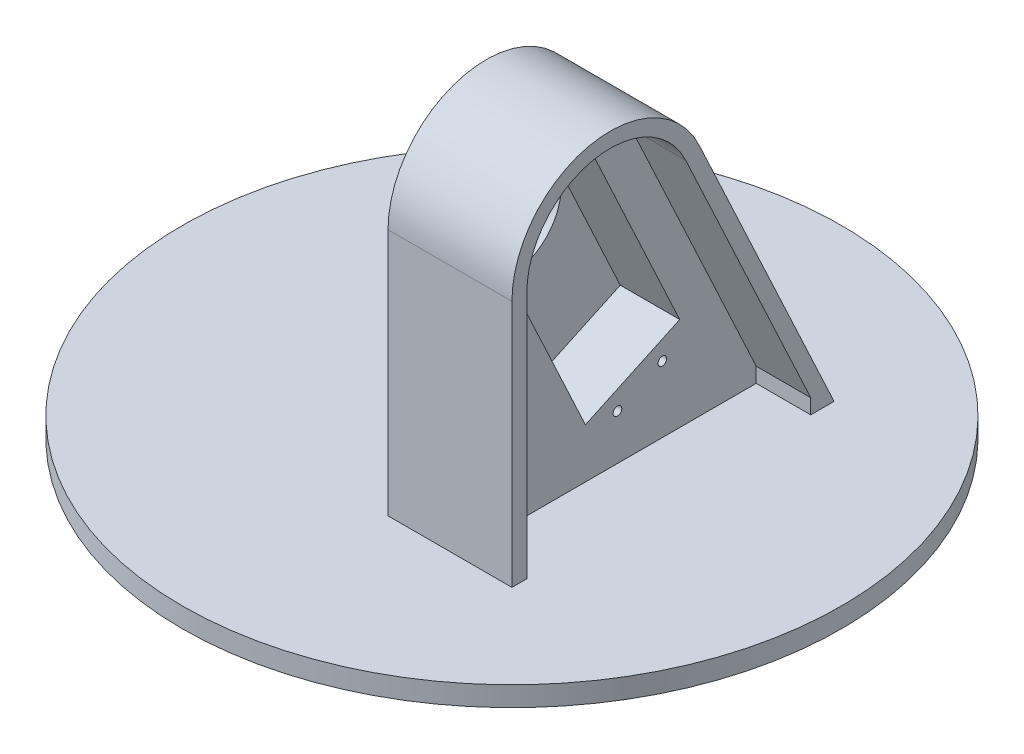
SolidWorks part; units mm, degrees
ref_plane "Front Plane" through (0, 0, 0) normal (0, 0, 1) x (1, 0, 0)
ref_plane "Top Plane" through (0, 0, 0) normal (0, 1, 0) x (1, 0, 0)
ref_plane "Right Plane" through (0, 0, 0) normal (1, 0, 0) x (0, 0, -1)
sketch "Sketch1" plane through (0, 0, 0) normal (0, 1, 0) x (1, 0, 0)
  circle A0 centre (0, 0) radius 66.5
  circle A1 centre (0, 0) radius 3.75
  circle A2 centre (0, -7.25) radius 0.875
  circle A3 centre (0, 7.25) radius 0.875
  dimension "D1" = 133
  dimension "D2" = 7.5
  dimension "D5" = 1.75
  dimension "D3" = 7.25
  dimension "D4" = 7.25
extrude "Boss-Extrude1" add sketch "Sketch1" against normal blind 4
ref_plane "Plane1" through (5, 0, 0) normal (1, 0, 0) x (0, 0, -1)
sketch "Sketch4" plane through (5, 0, 0) normal (1, 0, 0) x (0, 0, -1)
  line L0 (0, 0) -> (35, 0)
  line L1 (35, 0) -> (7.7791, 58.3754)
  line L2 (0, 0) -> (-30, 0)
  line L3 (-30, 0) -> (-30, 50)
  arc A0 (-30, 50) -> (7.7791, 58.3754) centre (-10.1821, 50) cw
  dimension "D1" = 65
  dimension "D2" = 35
  dimension "D3" = 30
  dimension "D4" = 50
extrude "Boss-Extrude2" add sketch "Sketch4" along normal blind 25 contours L3 A0 L1 L0 L2
sketch "Sketch5" plane through (30, 0, 0) normal (1, 0, 0) x (0, 0, -1)
  line L3 (-27, 3) -> (-27, 0)
  line L4 (35, 0) -> (-30, 0) construction
  line L5 (-27, 0) -> (30.2909, 0)
  line L6 (-27, 3) -> (30.2909, 3)
  line L7 (30.2909, 3) -> (5.0602, 57.1076)
  line L8 (-27, 50) -> (-27, 3)
  line L10 (30.2909, 3) -> (5.0602, 57.1076)
  line L11 (-27, 50) -> (-27, 3)
  line L12 (30.2909, 0) -> (30.2909, 3)
  arc A2 (5.0602, 57.1076) -> (-27, 50) centre (-10.1821, 50) ccw
  arc A3 (5.0602, 57.1076) -> (-27, 50) centre (-10.1821, 50) ccw
  dimension "D1" = 3
extrude "Cut-Extrude1" cut sketch "Sketch5" against normal blind 11
sketch "Sketch6" plane through (19, 0, 0) normal (1, 0, 0) x (0, 0, -1)
  line L0 (-21.5, 47.1586) -> (-2.4675, 56.0336)
  line L1 (-2.4675, 56.0336) -> (14.8598, 18.875)
  line L2 (14.8598, 18.875) -> (-4.1727, 10)
  line L3 (-4.1727, 10) -> (-21.5, 47.1586)
  line L4 (-27, 0) -> (30.2909, 0) construction
  line L5 (-27, 50) -> (-27, 0) construction
  line L11 (-2.4675, 56.0336) -> (-4.1727, 10) construction
  line L12 (-17.9945, 52.6551) -> (-8.9314, 56.8813)
  line L13 (-8.9314, 56.8813) -> (11.3543, 13.3785)
  line L14 (11.3543, 13.3785) -> (2.2912, 9.1523)
  line L15 (2.2912, 9.1523) -> (-17.9945, 52.6551)
  line L16 (-8.9314, 56.8813) -> (2.2912, 9.1523) construction
  circle A1 centre (-17.9945, 52.6551) radius 0.875
  circle A6 centre (-8.9314, 56.8813) radius 0.875
  circle A7 centre (11.3543, 13.3785) radius 0.875
  circle A8 centre (2.2912, 9.1523) radius 0.875
  point P10 (-3.3201, 33.0168)
  point P13 (-3.3201, 33.0168)
  dimension "D6" = 10
  dimension "D8" = 1.75
  dimension "D1" = 21
  dimension "D2" = 41
  dimension "D3" = 65
  dimension "D4" = 10
  dimension "D5" = 5.5
  dimension "D7" = 48
extrude "Cut-Extrude2" cut sketch "Sketch6" against normal blind 12 contours L2 L15 L0 L3 | L15 L2 L13 L0 | L0 L13 L2 L1 region at (19, 29.7415, 10.344) region at (19, 33.0168, 3.3201) region at (19, 36.2921, -3.7038)
extrude "Cut-Extrude3" cut sketch "Sketch6<3>" against normal blind 8 contours A1 | A6 | A8 | A7
sketch "Sketch6<3>" plane through (19, 0, 0) normal (1, 0, 0) x (0, 0, -1) same geometry as "Sketch6"
sketch "Sketch7" plane through (7, 0, 0) normal (1, 0, 0) x (0, 0, -1)
  line L0 (-21.5, 47.1586) -> (-2.4675, 56.0336) construction
  line L1 (-2.4675, 56.0336) -> (14.8598, 18.875) construction
  line L2 (-4.1727, 10) -> (-21.5, 47.1586) construction
  circle A0 centre (-7.5463, 42.0799) radius 10.5
extrude "Cut-Extrude4" cut sketch "Sketch7" against normal through all
sketch "Sketch8" plane through (0, 0, 0) normal (0, 1, 0) x (1, 0, 0)
  line L0 (0, 27) -> (-7.5, 27)
  line L1 (-7.5, 27) -> (-7.5, 37)
  line L2 (-7.5, 37) -> (0, 37)
  line L3 (0, 37) -> (0, 27)
  line L4 (30, 35) -> (5, 35) construction
  dimension "D1" = 7.5
  dimension "D2" = 10
  dimension "D3" = 2
extrude "Boss-Extrude3" add sketch "Sketch8" along normal blind 8
sketch "Sketch9" plane through (-7.5, 0, 0) normal (-1, 0, 0) x (0, 0, 1)
  line L8 (-35, 2) -> (-29, 2)
  line L9 (-29, 2) -> (-29, 6)
  line L10 (-29, 6) -> (-35, 6)
  line L11 (-35, 6) -> (-35, 2)
  line L12 (-35, 2) -> (-29, 2)
  line L13 (-29, 2) -> (-29, 6)
  line L14 (-29, 6) -> (-35, 6)
  line L15 (-35, 6) -> (-35, 2)
  dimension "D1" = 2
extrude "Cut-Extrude5" cut sketch "Sketch9" against normal blind 8
sketch "Sketch10" plane through (0, 8, 0) normal (0, 1, 0) x (1, 0, 0)
  line L0 (0, 33) -> (-7.5, 33)
  line L4 (0, 35) -> (-7.5, 35)
  line L5 (-7.5, 35) -> (-7.5, 29)
  line L6 (-7.5, 29) -> (0, 29)
  line L7 (0, 29) -> (0, 35)
  line L8 (0, 35) -> (-7.5, 35)
  line L9 (-7.5, 35) -> (-7.5, 33)
  line L11 (0, 33) -> (0, 35)
  dimension "D2" = 2
  dimension "D1" = 0
extrude "Cut-Extrude6" cut sketch "Sketch10" against normal up to next
